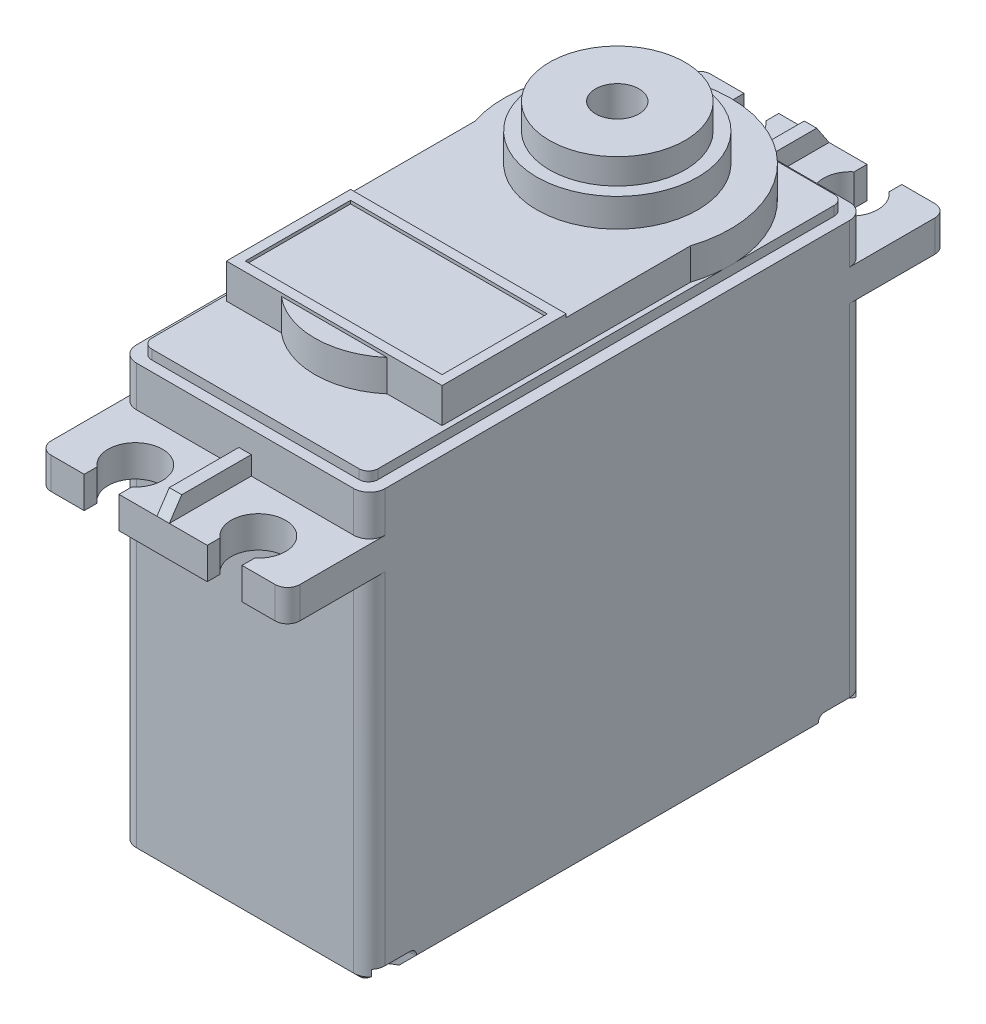
SolidWorks part; units mm, degrees
material "PBT General Purpose"
ref_plane "Front" through (0, 0, 0) normal (0, 0, 1) x (1, 0, 0)
ref_plane "Top" through (0, 0, 0) normal (0, 1, 0) x (1, 0, 0)
ref_plane "Right" through (0, 0, 0) normal (1, 0, 0) x (0, 0, -1)
sketch "Sketch1" plane through (0, 0, 0) normal (0, 1, 0) x (1, 0, 0)
  line L0 (0, 13.7537) -> (0, -13.7537) construction
  line L1 (13.7537, 0) -> (-13.7537, 0) construction
  line L2 (10.02, 19.97) -> (-10.02, 19.97)
  line L3 (-10.02, 19.97) -> (-10.02, -19.97)
  line L4 (10.02, 19.97) -> (10.02, -19.97)
  line L5 (10.02, -19.97) -> (-10.02, -19.97)
  point P6 (0, 0)
  point P8 (0, -19.97)
  point P11 (0, 19.97)
  point P12 (10.02, 0)
  point P13 (-10.02, 0)
  dimension "D1" = 20.04
  dimension "D2" = 39.94
extrude "Boss-Extrude1" add sketch "Sketch1" along normal blind 38.36
ref_plane "Plane1" through (0, 29.01, 0) normal (0, 1, 0) x (1, 0, 0)
sketch "Sketch2" plane through (0, 29.01, 0) normal (0, 1, 0) x (1, 0, 0)
  line L0 (0, 19.97) -> (0, -19.97) construction
  line L1 (10.02, 19.97) -> (-10.02, 19.97) construction
  line L2 (-10.02, -19.97) -> (10.02, -19.97) construction
  line L3 (-10.02, 19.97) -> (-10.02, 26.57)
  line L4 (10.02, 19.97) -> (10.02, 26.57)
  line L5 (-10.02, 26.57) -> (10.02, 26.57)
  line L6 (-10.02, 0) -> (10.02, 0) construction
  line L7 (-10.02, 19.97) -> (-10.02, -19.97) construction
  line L8 (10.02, -19.97) -> (10.02, 19.97) construction
  line L9 (10.02, -19.97) -> (10.02, -26.57)
  line L10 (-10.02, -19.97) -> (-10.02, -26.57)
  line L11 (-10.02, -26.57) -> (10.02, -26.57)
  line L12 (-10.02, 19.97) -> (10.02, 19.97)
  line L13 (-10.02, -19.97) -> (10.02, -19.97)
  dimension "D1" = 6.6
extrude "Boss-Extrude2" add sketch "Sketch2" along normal blind 2.54
ref_plane "Plane2" through (0, 31.55, 0) normal (0, 1, 0) x (1, 0, 0)
sketch "Sketch3" plane through (0, 31.55, 0) normal (0, 1, 0) x (1, 0, 0)
  line L0 (0, 26.57) -> (0, -26.57) construction
  line L1 (10.02, 26.57) -> (-10.02, 26.57) construction
  line L2 (-10.02, -26.57) -> (10.02, -26.57) construction
  line L3 (-4.955, 26.57) -> (-4.955, -26.57) construction
  line L4 (6.355, 26.57) -> (3.555, 26.57)
  line L5 (-6.355, 26.57) -> (-6.355, 25.5391)
  line L6 (-3.555, 26.57) -> (-3.555, 25.5391)
  line L7 (-6.355, 26.57) -> (-3.555, 26.57)
  line L8 (3.555, 26.57) -> (3.555, 25.5391)
  line L9 (6.355, 26.57) -> (6.355, 25.5391)
  arc A0 (-6.355, 25.5391) -> (-3.555, 25.5391) centre (-4.955, 23.855) ccw
  arc A1 (6.355, 25.5391) -> (3.555, 25.5391) centre (4.955, 23.855) cw
  dimension "D2" = 4.38
  dimension "D3" = 23.855
  dimension "D1" = 4.955
  dimension "D4" = 2.8
extrude "Cut-Extrude1" cut sketch "Sketch3" against normal blind 2.54
mirror "Mirror1" about plane through (0, 0, 0) normal (0, 0, 1) of "Cut-Extrude1"
ref_plane "Plane3" through (0, 31.55, 0) normal (0, 1, 0) x (1, 0, 0)
sketch "Sketch4" plane through (0, 31.55, 0) normal (0, 1, 0) x (1, 0, 0)
  line L0 (0, 26.57) -> (0, -26.57) construction
  line L1 (3.555, 26.57) -> (-3.555, 26.57) construction
  line L2 (-3.555, -26.57) -> (3.555, -26.57) construction
  line L3 (-0.5, 26.57) -> (-0.5, 19.97)
  line L4 (-10.02, 19.97) -> (10.02, 19.97) construction
  line L5 (-0.5, 19.97) -> (0.5, 19.97)
  line L6 (10.02, 19.97) -> (-10.02, 19.97) construction
  line L7 (-0.5, 26.57) -> (0.5, 26.57)
  line L8 (0.5, 26.57) -> (0.5, 19.97)
  line L9 (-10.02, 0) -> (10.02, 0) construction
  line L10 (-10.02, 19.97) -> (-10.02, -19.97) construction
  line L11 (10.02, -19.97) -> (10.02, 19.97) construction
  line L12 (0.5, -26.57) -> (0.5, -19.97)
  line L13 (-0.5, -26.57) -> (0.5, -26.57)
  line L14 (-0.5, -19.97) -> (0.5, -19.97)
  line L15 (-0.5, -26.57) -> (-0.5, -19.97)
  point P14 (0, 19.97)
  point P25 (0, -19.97)
  dimension "D1" = 1
extrude "Boss-Extrude3" add sketch "Sketch4" along normal blind 1.5
ref_plane "Plane4" through (-0.5, 0, 0) normal (-1, 0, 0) x (0, 0, 1)
sketch "Sketch5" plane through (-0.5, 0, 0) normal (-1, 0, 0) x (0, 0, 1)
  line L0 (0, 38.36) -> (0, 0) construction
  line L1 (-19.97, 38.36) -> (19.97, 38.36) construction
  line L2 (-26.57, 31.55) -> (-25.57, 33.05)
  line L3 (-26.57, 33.05) -> (-19.97, 33.05) construction
  line L4 (-25.57, 33.05) -> (-26.57, 33.05)
  line L5 (-26.57, 33.05) -> (-26.57, 31.55) construction
  line L6 (-26.57, 33.05) -> (-26.57, 31.55)
  line L7 (26.57, 33.05) -> (26.57, 31.55)
  line L8 (25.57, 33.05) -> (26.57, 33.05)
  line L9 (26.57, 31.55) -> (25.57, 33.05)
  dimension "D1" = 1
extrude "Cut-Extrude2" cut sketch "Sketch5" against normal up to surface (1 mm away) up to face at (0.5, 32.3, -23.27)
ref_plane "Plane5" through (0, 38.36, 0) normal (0, 1, 0) x (1, 0, 0)
sketch "Sketch6" plane through (0, 38.36, 0) normal (0, 1, 0) x (1, 0, 0)
  line L0 (-10.02, 19.97) -> (-10.02, -19.97)
  line L1 (-10.02, -19.97) -> (10.02, -19.97)
  line L2 (10.02, -19.97) -> (10.02, 19.97) construction
  line L3 (-10.02, -19.97) -> (10.02, -19.97) construction
  line L4 (10.02, -19.97) -> (10.02, 19.97)
  line L5 (10.02, 19.97) -> (-10.02, 19.97)
extrude "Cut-Extrude3" cut sketch "Sketch6" against normal blind 3.55
ref_plane "Plane6" through (0, 34.81, 0) normal (0, 1, 0) x (1, 0, 0)
sketch "Sketch7" plane through (0, 34.81, 0) normal (0, 1, 0) x (1, 0, 0)
  line L0 (0, 19.97) -> (0, -19.97) construction
  line L1 (10.02, 19.97) -> (-10.02, 19.97) construction
  line L2 (-10.02, -19.97) -> (10.02, -19.97) construction
  line L3 (-10.02, 0) -> (10.02, 0) construction
  line L4 (-10.02, 19.97) -> (-10.02, -19.97) construction
  line L5 (10.02, -19.97) -> (10.02, 19.97) construction
  line L6 (-9.11, 19.136) -> (-9.11, -19.136)
  line L7 (9.11, 19.136) -> (9.11, -19.136)
  line L8 (-9.11, 19.136) -> (9.11, 19.136)
  line L9 (-9.11, -19.136) -> (9.11, -19.136)
  point P15 (-9.11, 0)
  point P18 (9.11, 0)
  dimension "D1" = 19.136
  dimension "D2" = 18.22
extrude "Boss-Extrude4" add sketch "Sketch7" along normal blind 0.762
fillet "Fillet1" radius 1.27 8 edges
fillet "Fillet2" radius 0.762 4 edges at (9.11, 35.191, -19.136) (-9.11, 35.191, -19.136) (-9.11, 35.191, 19.136) (9.11, 35.191, 19.136)
ref_plane "Plane7" through (0, 35.572, 0) normal (0, 1, 0) x (1, 0, 0)
sketch "Sketch8" plane through (0, 35.572, 0) normal (0, 1, 0) x (1, 0, 0)
  line L0 (0, 19.136) -> (0, -19.136) construction
  line L1 (8.348, 19.136) -> (-8.348, 19.136) construction
  line L2 (-8.348, -19.136) -> (8.348, -19.136) construction
  line L3 (8.6857, 7.214) -> (8.6857, -12.786)
  line L4 (-8.348, -19.136) -> (8.348, -19.136) construction
  line L6 (-8.6857, 7.214) -> (-8.6857, -12.786)
  line L7 (-8.6857, -12.786) -> (8.6857, -12.786)
  arc A0 (8.6857, 7.214) -> (-8.6857, 7.214) centre (0, 10.011) ccw
  point P2 (0, 19.136)
  dimension "D1" = 18.25
  dimension "D2" = 20
  dimension "D3" = 6.35
extrude "Boss-Extrude5" add sketch "Sketch8" along normal blind 2.54
ref_plane "Plane8" through (0, 38.112, 0) normal (0, 1, 0) x (1, 0, 0)
sketch "Sketch10" plane through (0, 38.112, 0) normal (0, 1, 0) x (1, 0, 0)
  line L0 (0, 19.136) -> (0, -12.786) construction
  line L1 (-8.6857, -12.786) -> (8.6857, -12.786) construction
  arc A0 (8.6857, 7.214) -> (-8.6857, 7.214) centre (0, 10.011) ccw construction
  circle A1 centre (0, 10.011) radius 6.477
  dimension "D1" = 12.954
extrude "Boss-Extrude6" add sketch "Sketch10" along normal blind 2.286
sketch "Sketch11" plane through (0, 40.398, 0) normal (0, 1, 0) x (1, 0, 0)
  circle A0 centre (0, 10.011) radius 5.461
  dimension "D1" = 10.922
extrude "Boss-Extrude7" add sketch "Sketch11" along normal blind 2.0508
sketch "Sketch12" plane through (0, 42.4488, 0) normal (0, 1, 0) x (1, 0, 0)
  circle A0 centre (0, 10.011) radius 1.75
  dimension "D1" = 3.5
extrude "Cut-Extrude4" cut sketch "Sketch12" against normal blind 2.54
sketch "Sketch13" plane through (0, 38.112, 0) normal (0, 1, 0) x (1, 0, 0)
  line L0 (-8.6857, -12.786) -> (-8.6857, -2.786)
  line L1 (-8.6857, 7.214) -> (-8.6857, -12.786) construction
  line L2 (-8.6857, -2.786) -> (8.6857, -2.786)
  line L3 (8.6857, -12.786) -> (8.6857, 7.214) construction
  line L4 (8.6857, -2.786) -> (8.6857, -12.786)
  line L5 (8.6857, -12.786) -> (-8.6857, -12.786)
  line L6 (0, -2.786) -> (0, -12.786) construction
  line L7 (-8.6857, -7.786) -> (8.6857, -7.786) construction
  line L8 (-7.9237, -3.548) -> (-7.9237, -12.024)
  line L9 (-7.9237, -3.548) -> (7.9237, -3.548)
  line L10 (-7.9237, -12.024) -> (7.9237, -12.024)
  line L11 (7.9237, -3.548) -> (7.9237, -12.024)
  point P18 (-7.9237, -7.786)
  point P20 (0, -12.024)
  point P21 (0, -3.548)
  dimension "D1" = 0.762
  dimension "D2" = 0.762
extrude "Boss-Extrude8" add sketch "Sketch13" along normal blind 0.254
ref_plane "Plane9" through (0, 35.572, 0) normal (0, 1, 0) x (1, 0, 0)
sketch "Sketch14" plane through (0, 35.572, 0) normal (0, 1, 0) x (1, 0, 0)
  line L0 (0, -12.786) -> (0, -19.136) construction
  line L1 (-8.6857, -12.786) -> (8.6857, -12.786) construction
  line L2 (-8.348, -19.136) -> (8.348, -19.136) construction
  line L3 (-7.9237, -7.786) -> (7.9237, -7.786) construction
  line L4 (-7.9237, -3.548) -> (-7.9237, -12.024) construction
  line L5 (7.9237, -12.024) -> (7.9237, -3.548) construction
  line L6 (-4.2604, -12.786) -> (4.2604, -12.786)
  arc A0 (-4.2604, -12.786) -> (4.2604, -12.786) centre (0, -7.786) ccw
  dimension "D2" = 6.5689
  dimension "D1" = 12.786
extrude "Boss-Extrude9" add sketch "Sketch14" along normal blind 2.54
ref_plane "Plane10" through (0, 0, 0) normal (0, -1, 0) x (-1, 0, 0)
sketch "Sketch15" plane through (0, 0, 0) normal (0, -1, 0) x (-1, 0, 0)
  line L0 (0, -19.97) -> (0, 19.97) construction
  line L1 (-8.75, -19.97) -> (8.75, -19.97) construction
  line L2 (-8.75, 19.97) -> (8.75, 19.97) construction
  line L3 (10.02, 0) -> (-10.02, 0) construction
  line L4 (10.02, 18.7) -> (10.02, -18.7) construction
  line L5 (-10.02, -18.7) -> (-10.02, 18.7) construction
  line L6 (6.5737, -19.5213) -> (10.02, -19.5213)
  line L7 (10.02, -18.7) -> (10.02, -26.57) construction
  line L8 (10.02, -19.5213) -> (10.02, -16.1801)
  line L9 (-10.02, -19.5213) -> (-10.02, -16.1801)
  line L10 (-6.5737, -19.5213) -> (-10.02, -19.5213)
  line L11 (-6.5737, 19.5213) -> (-10.02, 19.5213)
  line L12 (-10.02, 19.5213) -> (-10.02, 16.1801)
  line L13 (10.02, 19.5213) -> (10.02, 16.1801)
  line L14 (6.5737, 19.5213) -> (10.02, 19.5213)
  arc A0 (10.02, -16.1801) -> (6.5737, -19.5213) centre (11.35, -21) ccw
  arc A1 (-10.02, -16.1801) -> (-6.5737, -19.5213) centre (-11.35, -21) cw
  arc A2 (-10.02, 16.1801) -> (-6.5737, 19.5213) centre (-11.35, 21) ccw
  arc A3 (10.02, 16.1801) -> (6.5737, 19.5213) centre (11.35, 21) cw
  dimension "D3" = 10
  dimension "D1" = 11.35
  dimension "D2" = 21
  dimension "D4" = 3.4463
extrude "Cut-Extrude5" cut sketch "Sketch15" against normal blind 1.524
sketch "Sketch16" plane through (0, 0, 0) normal (0, -1, 0) x (-1, 0, 0)
  line L0 (0, -19.97) -> (0, 19.97) construction
  line L1 (8.75, -19.97) -> (-8.75, -19.97) construction
  line L2 (8.75, 19.97) -> (-8.75, 19.97) construction
  line L3 (10.02, 0) -> (-10.02, 0) construction
  line L4 (10.02, 16.1801) -> (10.02, -16.1801) construction
  line L5 (-10.02, -16.1801) -> (-10.02, 16.1801) construction
  circle A0 centre (8.75, -18.7) radius 0.5
  circle A1 centre (-8.75, -18.7) radius 0.5
  circle A2 centre (-8.75, 18.7) radius 0.5
  circle A3 centre (8.75, 18.7) radius 0.5
  dimension "D1" = 1
extrude "Cut-Extrude6" cut sketch "Sketch16" against normal blind 6
chamfer "Chamfer1" distance 1 angle 45 8 edges at (0, 0, -19.97) (10.02, 0, 0) (0, 0, 19.97) (-10.02, 0, 0) (9.2838, 0, -19.8524) (-9.2838, 0, -19.8524) (-9.2838, 0, 19.8524) (9.2838, 0, 19.8524)
fillet "Fillet3" radius 0.5 4 edges at (-7.8697, 1.524, 17.4101) (7.8697, 1.524, 17.4101) (7.8697, 1.524, -17.4101) (-7.8697, 1.524, -17.4101)
ref_plane "Plane13" through (0, 0, -19.97) normal (0, 0, -1) x (-1, 0, 0)
sketch "Sketch17" plane through (0, 0, -19.97) normal (0, 0, -1) x (-1, 0, 0)
  line L0 (0, 1) -> (0, 29.01) construction
  line L1 (-8.75, 1) -> (8.75, 1) construction
  line L2 (-3.555, 29.01) -> (3.555, 29.01) construction
  line L3 (-3.175, 1) -> (-3.175, 4.81)
  line L4 (-3.175, 4.81) -> (3.175, 4.81)
  line L5 (3.175, 1) -> (3.175, 4.81)
  line L6 (-3.175, 1) -> (3.175, 1)
  line L7 (0, 1.5) -> (-2.675, 1.5)
  line L8 (-2.675, 1.5) -> (-2.675, 4.31)
  line L9 (-2.675, 4.31) -> (0, 4.31)
  line L10 (0, 1.5) -> (2.675, 1.5)
  line L11 (2.675, 1.5) -> (2.675, 4.31)
  line L12 (2.675, 4.31) -> (0, 4.31)
  point P11 (0, 4.81)
  dimension "D1" = 6.35
  dimension "D2" = 3.81
  dimension "D4" = 0.5
  dimension "D5" = 0.5
  dimension "D6" = 0.5
extrude "Boss-Extrude10" add sketch "Sketch17" along normal blind 1.5
fillet "Fillet5" radius 0.5 4 edges at (-3.175, 4.81, -20.72) (-3.175, 1, -20.72) (3.175, 1, -20.72) (3.175, 4.81, -20.72)
fillet "Fillet6" radius 1 4 edges at (10.02, 30.28, 26.57) (10.02, 30.28, -26.57) (-10.02, 30.28, 26.57) (-10.02, 30.28, -26.57)
ref_plane "Plane14" through (9.11, 35.572, 18.374) normal (0, 0, -1) x (-1, 0, 0)
sketch "Sketch19" plane through (10.02, 0, 0) normal (1, 0, 0) x (0, 0, -1)
  line L0 (14.9859, 0) -> (14.9859, 40.398)
  line L1 (16.5761, 0) -> (-16.5761, 0) construction
  line L2 (16.488, 40.398) -> (3.534, 40.398) construction
  line L3 (11.1134, 45.4968) -> (11.1134, 40.398)
  line L4 (10.7543, 45.4968) -> (11.2355, 45.4968) construction
  dimension "D1" = 40.398
  dimension "D2" = 5.0988
